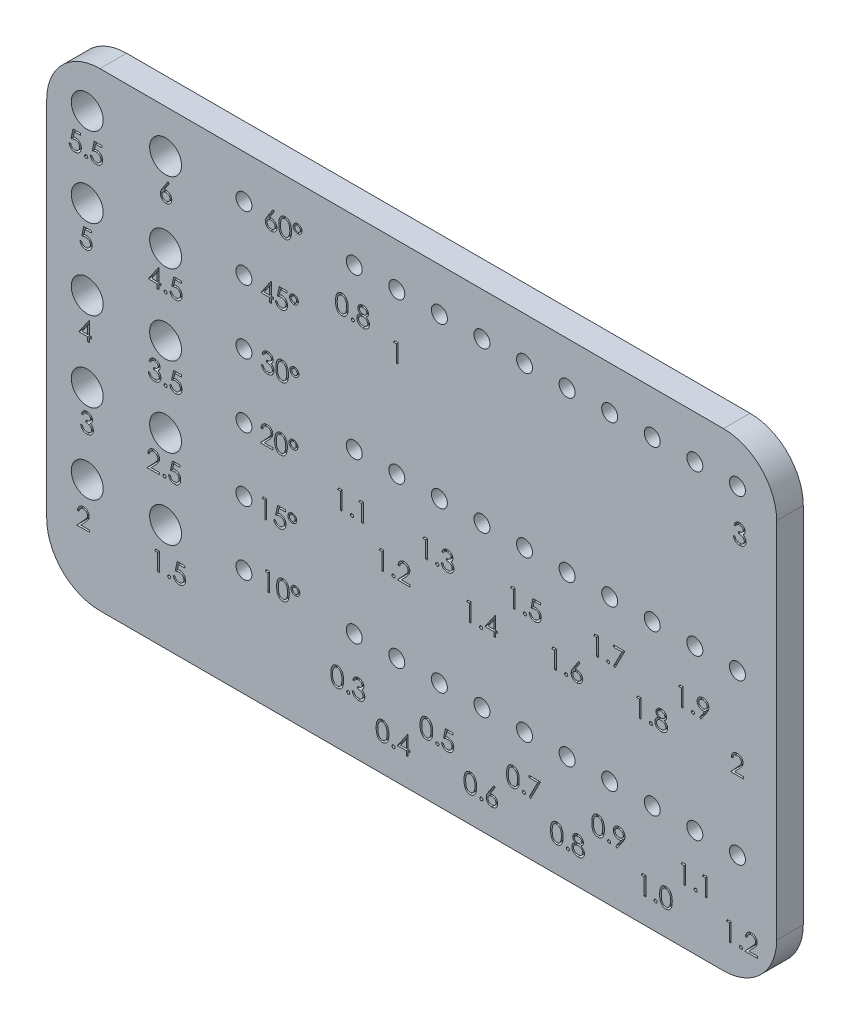
SolidWorks part; units mm, degrees
ref_plane "Front Plane" through (0, 0, 0) normal (0, 0, 1) x (1, 0, 0)
ref_plane "Top Plane" through (0, 0, 0) normal (0, 1, 0) x (1, 0, 0)
ref_plane "Right Plane" through (0, 0, 0) normal (1, 0, 0) x (0, 0, -1)
sketch "Sketch1" plane through (0, 0, 0) normal (0, 0, 1) x (1, 0, 0)
  line L0 (0, 0) -> (0, 52.8809) construction
  line L1 (0, 0) -> (35.6862, 0) construction
  line L2 (0, 15) -> (39.9349, 15) construction
  line L3 (0, -15) -> (39.9349, -15) construction
  line L4 (-71.4458, 30) -> (-71.4458, -30) construction
  line L5 (-56.7239, 30) -> (-56.7239, -30) construction
  line L6 (36, 30) -> (0, 30) construction
  line L7 (-86.1678, 30) -> (-86.1678, -30) construction
  line L9 (-93.7786, -50.1331) -> (43.3782, -50.1331)
  line L10 (-93.7786, -50.1331) -> (-93.7786, 38.0928)
  line L11 (-93.7786, 38.0928) -> (43.3782, 38.0928)
  line L12 (43.3782, -50.1331) -> (43.3782, 38.0928)
  circle A0 centre (4, 0) radius 1.5
  circle A1 centre (12, 0) radius 1.5
  circle A2 centre (20, 0) radius 1.5
  circle A3 centre (28, 0) radius 1.5
  circle A4 centre (36, 0) radius 1.5
  circle A5 centre (-36, 0) radius 1.5
  circle A6 centre (-28, 0) radius 1.5
  circle A7 centre (-20, 0) radius 1.5
  circle A8 centre (-12, 0) radius 1.5
  circle A9 centre (-4, 0) radius 1.5
  circle A10 centre (-4, -30) radius 1.5
  circle A11 centre (-12, -30) radius 1.5
  circle A12 centre (-20, -30) radius 1.5
  circle A13 centre (-28, -30) radius 1.5
  circle A14 centre (-36, -30) radius 1.5
  circle A15 centre (36, -30) radius 1.5
  circle A16 centre (28, -30) radius 1.5
  circle A17 centre (20, -30) radius 1.5
  circle A18 centre (12, -30) radius 1.5
  circle A19 centre (4, -30) radius 1.5
  circle A20 centre (-4, 30) radius 1.5
  circle A21 centre (-12, 30) radius 1.5
  circle A22 centre (-20, 30) radius 1.5
  circle A23 centre (-28, 30) radius 1.5
  circle A24 centre (-36, 30) radius 1.5
  circle A25 centre (36, 30) radius 1.5
  circle A26 centre (28, 30) radius 1.5
  circle A27 centre (20, 30) radius 1.5
  circle A28 centre (12, 30) radius 1.5
  circle A29 centre (4, 30) radius 1.5
  circle A30 centre (-86.1678, -30) radius 3
  circle A31 centre (-71.4458, -30) radius 3
  circle A32 centre (-71.4458, 0) radius 3
  circle A33 centre (-71.4458, -15) radius 3
  circle A34 centre (-86.1678, -15) radius 3
  circle A35 centre (-86.1678, 0) radius 3
  circle A36 centre (-86.1678, 15) radius 3
  circle A37 centre (-71.4458, 15) radius 3
  circle A38 centre (-86.1678, 30) radius 3
  circle A39 centre (-71.4458, 30) radius 3
  circle A45 centre (-56.7239, 30) radius 1.5
  circle A46 centre (-56.7239, 18) radius 1.5
  circle A48 centre (-56.7239, -18) radius 1.5
  circle A49 centre (-56.7239, -30) radius 1.5
  circle A50 centre (-56.7239, -6) radius 1.5
  circle A51 centre (-56.7239, 6) radius 1.5
  text T0 "0.8"
  text T1 "1"
  text T2 "3"
  text T3 "1.5\r\n"
  text T4 "2"
  text T5 "2.5"
  text T6 "3"
  text T7 "4"
  text T8 "4.5"
  text T9 "5"
  text T10 "3.5"
  text T11 "5.5"
  text T12 "6"
  text T13 "1.1"
  text T14 "1.2"
  text T15 "1.3"
  text T16 "1.4"
  text T17 "1.5"
  text T18 "1.6"
  text T19 "1.7"
  text T20 "1.8"
  text T21 "1.9"
  text T22 "2"
  text T23 "0.3"
  text T24 "0.4"
  text T25 "0.5"
  text T26 "0.6"
  text T27 "0.7"
  text T28 "0.8"
  text T29 "0.9"
  text T30 "1.0"
  text T31 "1.1"
  text T32 "1.2"
  text T33 "10°"
  text T34 "60°"
  text T35 "45°\r\n"
  text T36 "30°"
  text T37 "20°"
  text T38 "15°"
  point P111 (-29.2999, 18)
  point P113 (0, 0)
  dimension "D1" = 3
  dimension "D8" = 6
  dimension "D2" = 8
  dimension "D3" = 4
  dimension "D4" = 8
  dimension "D5" = 8
  dimension "D6" = 8
  dimension "D7" = 15
  dimension "D10" = 12
  dimension "D11" = 12
  dimension "D12" = 12
  dimension "D13" = 12
  dimension "D14" = 12
extrude "Boss-Extrude1" add sketch "Sketch1" along normal blind 5
fillet "Fillet1" radius 10 4 edges at (43.3782, -50.1331, 2.5) (43.3782, 38.0928, 2.5) (-93.7786, -50.1331, 2.5) (-93.7786, 38.0928, 2.5)
